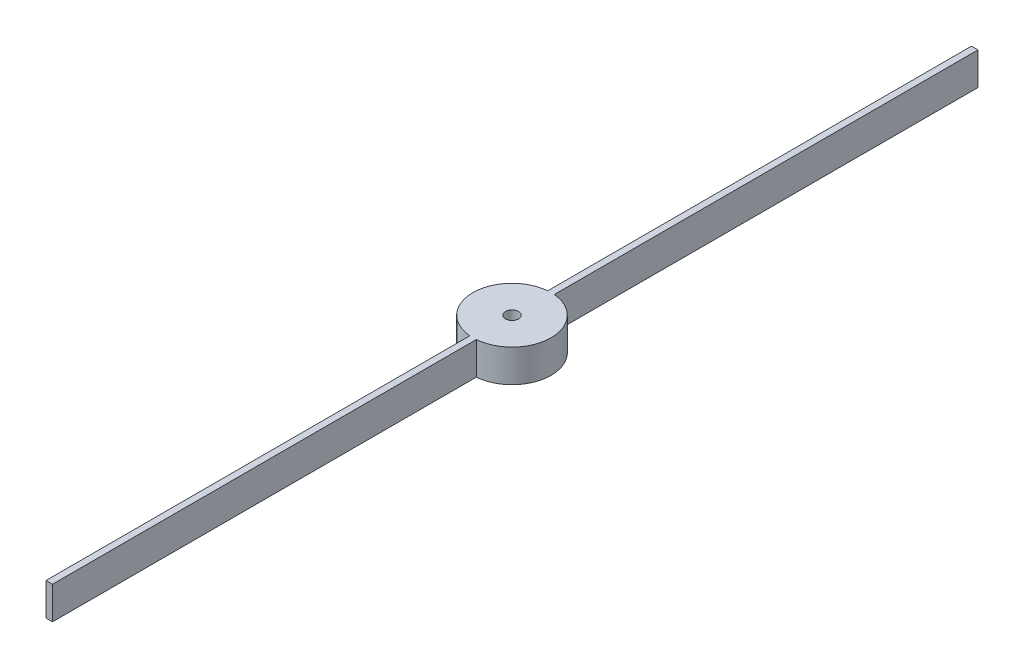
SolidWorks part; units mm, degrees
ref_plane "Front Plane" through (0, 0, 0) normal (0, 0, 1) x (1, 0, 0)
ref_plane "Top Plane" through (0, 0, 0) normal (0, 1, 0) x (1, 0, 0)
ref_plane "Right Plane" through (0, 0, 0) normal (1, 0, 0) x (0, 0, -1)
sketch "Sketch1" plane through (0, 0, 0) normal (0, 1, 0) x (1, 0, 0)
  line L0 (-1, 11.9583) -> (-1, 141.9583)
  line L1 (-1, -11.9583) -> (-1, -141.9583)
  line L2 (1, -11.9583) -> (1, -141.9583)
  line L3 (-1, -141.9583) -> (1, -141.9583)
  line L4 (1, 11.9583) -> (1, 141.9583)
  line L5 (1, 141.9583) -> (-1, 141.9583)
  circle A0 centre (0, 0) radius 2
  arc A5 (-1, 11.9583) -> (-1, -11.9583) centre (0, 0) ccw
  arc A6 (1, -11.9583) -> (1, 11.9583) centre (0, 0) ccw
  point P24 (0, 0)
  dimension "D1" = 4
  dimension "D2" = 130
  dimension "D3" = 2
extrude "Boss-Extrude1" add sketch "Sketch1" along normal blind 10
